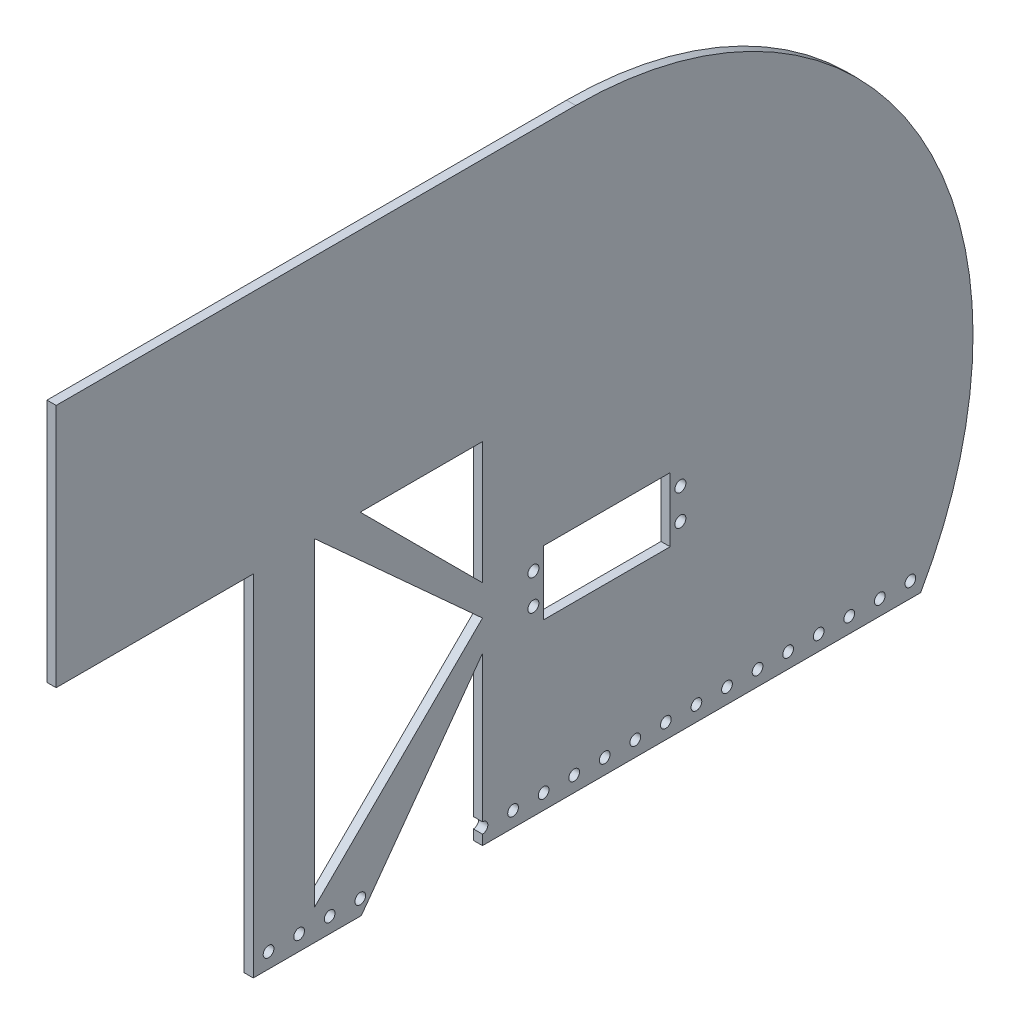
SolidWorks part; units mm, degrees
ref_plane "Front Plane" through (0, 0, 0) normal (0, 0, 1) x (1, 0, 0)
ref_plane "Top Plane" through (0, 0, 0) normal (0, 1, 0) x (1, 0, 0)
ref_plane "Right Plane" through (0, 0, 0) normal (1, 0, 0) x (0, 0, -1)
sketch "Sketch1" plane through (0, 0, 0) normal (1, 0, 0) x (0, 0, -1)
  line L0 (0, 130) -> (-170, 130)
  line L1 (-170, 130) -> (-170, 50)
  line L2 (-170, 50) -> (-120, 50)
  arc A0 (-120, 50) -> (0, 130) centre (0, 0) ccw
  circle A1 centre (0, 0) radius 5
  dimension "D1" = 260
  dimension "D2" = 10
  dimension "D3" = 80
  dimension "D4" = 170
extrude "Boss-Extrude1" add sketch "Sketch1" along normal blind 3
sketch "Sketch2" plane through (3, 0, 0) normal (1, 0, 0) x (0, 0, -1)
  line L0 (-10, 10) -> (-10, -10) construction
  line L1 (-10, -10) -> (30.4, -10) construction
  line L2 (30.4, -10) -> (30.4, 10) construction
  line L3 (30.4, 10) -> (-10, 10) construction
  line L4 (30.9, 10.5) -> (-10.5, 10.5)
  line L5 (-10.5, 10.5) -> (-10.5, -10.5)
  line L6 (-10.5, -10.5) -> (30.9, -10.5)
  line L7 (30.9, -10.5) -> (30.9, 10.5)
  circle A1 centre (0, 0) radius 5 construction
  circle A2 centre (-13.85, 5) radius 1.8
  circle A3 centre (-13.85, -5) radius 1.8
  circle A4 centre (34.25, 5) radius 1.8
  circle A5 centre (34.25, -5) radius 1.8
  point P11 (-10, 0)
  dimension "D1" = 10
  dimension "D2" = 10
  dimension "D4" = 3.6
  dimension "D7" = 3.85
  dimension "D8" = 5
  dimension "D10" = 5
  dimension "D12" = 3.85
  dimension "D13" = 10
  dimension "D3" = 40.4
  dimension "D5" = 20
  dimension "D9" = 10
  dimension "D11" = 3.85
  dimension "D6" = 0.5
extrude "ServoHole" cut sketch "Sketch2" against normal through all
sketch "Sketch3" plane through (3, 0, 0) normal (1, 0, 0) x (0, 0, -1)
  line L1 (123.9473, -130) -> (-198.7557, -130)
  line L2 (123.9473, -130) -> (123.9473, -64.5)
  line L3 (123.9473, -64.5) -> (-198.7557, -64.5)
  line L4 (-198.7557, -130) -> (-198.7557, -64.5)
  arc A0 (-120, 50) -> (0, 130) centre (0, 0) ccw construction
  dimension "D1" = 130
  dimension "D2" = 64.5
extrude "Cut-Extrude2" cut sketch "Sketch3" against normal through all
sketch "Sketch4" plane through (3, 0, 0) normal (1, 0, 0) x (0, 0, -1)
  line L1 (-170, 50) -> (-105.5, 50)
  line L2 (-170, 50) -> (-170, -65)
  line L3 (-170, -65) -> (-105.5, -65)
  line L4 (-30.5, 50) -> (-30.5, 10)
  line L5 (-10.5, 10.5) -> (-10.5, -10.5) construction
  line L6 (-70.5, 50) -> (-30.5, 10)
  line L7 (-85.5, 50) -> (-30.5, 0)
  line L8 (-30.5, 0) -> (-85.5, -54.5)
  line L9 (-30.5, -10) -> (-70.5, -65)
  line L10 (-70.5, 50) -> (-30.5, 50)
  line L11 (-30.5, -10) -> (-30.5, -65)
  line L12 (-70.5, -65) -> (-30.5, -65)
  line L13 (-85.5, 50) -> (-85.5, -54.5)
  line L14 (-105.5, 50) -> (-105.5, -65)
  line L15 (112.8705, -64.5) -> (-112.8705, -64.5) construction
  dimension "D1" = 20
  dimension "D2" = 40
  dimension "D3" = 45
  dimension "D4" = 10
  dimension "D5" = 10
  dimension "D6" = 15
  dimension "D7" = 20
  dimension "D8" = 40
  dimension "D9" = 20
  dimension "D10" = 10
  dimension "D11" = 115
extrude "Cut-Extrude5" cut sketch "Sketch4" against normal through all
sketch "Sketch5" plane through (3, 0, 0) normal (1, 0, 0) x (0, 0, -1)
  line L0 (112.8705, -64.5) -> (-30.5, -64.5) construction
  line L1 (-30.5, -64.5) -> (-30.5, -10) construction
  circle A0 centre (-20.5, -59.5) radius 1.75
  dimension "D1" = 3.5
  dimension "D2" = 5
  dimension "D3" = 10
extrude "Cut-Extrude6" cut sketch "Sketch5" against normal blind 10
pattern_linear "LPattern1" count 14 spacing 10 along (0, 0, -1) of "Cut-Extrude6"
pattern_linear "LPattern2" count 14 spacing 10 along (0, 0, 1) of "Cut-Extrude6"
